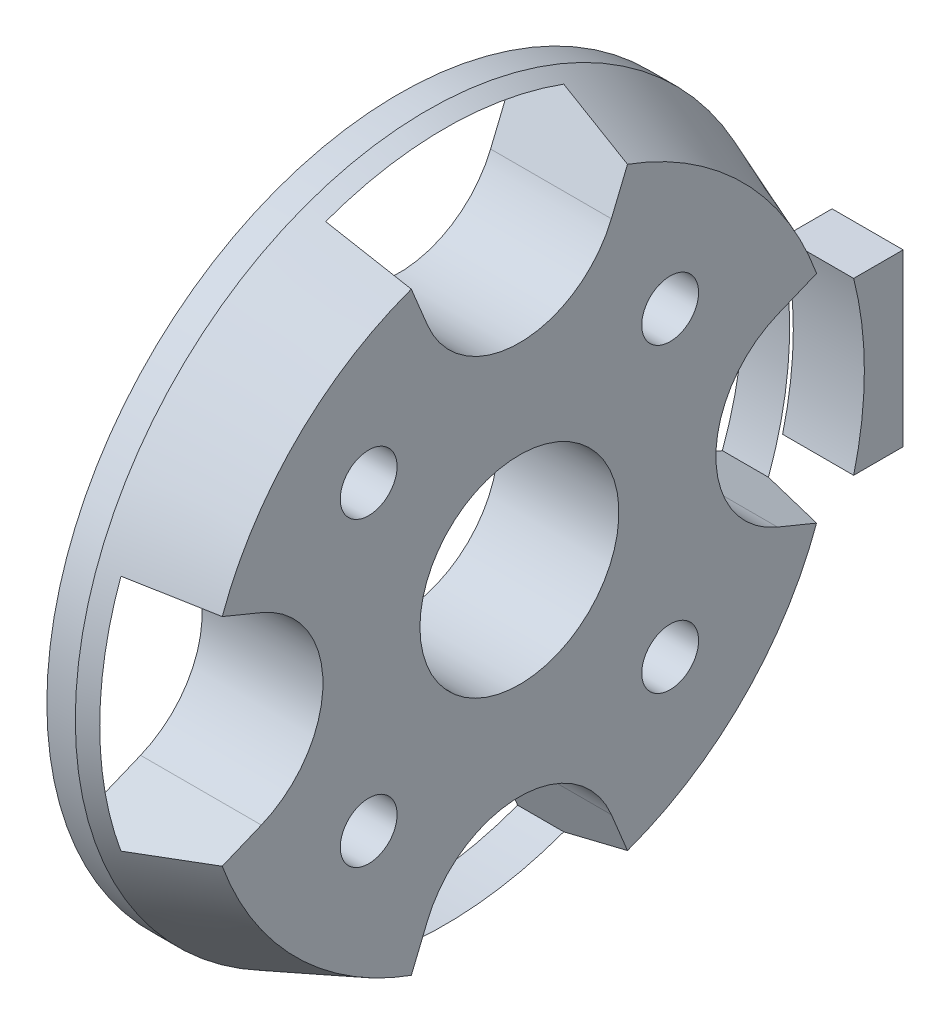
SolidWorks part; units mm, degrees
ref_plane "Front Plane" through (0, 0, 0) normal (0, 0, 1) x (1, 0, 0)
ref_plane "Top Plane" through (0, 0, 0) normal (0, 1, 0) x (1, 0, 0)
ref_plane "Right Plane" through (0, 0, 0) normal (1, 0, 0) x (0, 0, -1)
sketch "Sketch2" plane through (0, 0, 0) normal (0, 0, 1) x (1, 0, 0)
  line L0 (0, 0) -> (51.0154, 0) construction
  line L1 (0, 24.75) -> (2, 24.75)
  line L2 (2, 24.75) -> (8.5, 22.25)
  line L3 (8.5, 22.25) -> (8.5, 7)
  line L4 (8.5, 7) -> (0, 7)
  line L5 (0, 7) -> (0, 24.75)
  dimension "D1" = 8.5
  dimension "D2" = 2
  dimension "D3" = 2.5
  dimension "D4" = 14
  dimension "D5" = 49.5
revolve "Revolve1" add sketch "Sketch2" angle 360 about L0
sketch "Sketch3" plane through (8.5, 0, 0) normal (1, 0, 0) x (0, 0, -1)
  line L0 (0, 0) -> (10.6066, 10.6066) construction
  line L1 (0, 0) -> (5.0555, 0) construction
  circle A0 centre (10.6066, 10.6066) radius 2
  circle A1 centre (10.6066, -10.6066) radius 2
  circle A2 centre (-10.6066, -10.6066) radius 2
  circle A3 centre (-10.6066, 10.6066) radius 2
  point P14 (0, 0)
  dimension "D2" = 4
  dimension "D1" = 45
  dimension "D3" = 15
  dimension "D4" = 4
extrude "Cut-Extrude1" cut sketch "Sketch3" against normal blind 5
sketch "Sketch4" plane through (8.5, 0, 0) normal (1, 0, 0) x (0, 0, -1)
  line L0 (0, 0) -> (15, 0) construction
  line L1 (15, 6) -> (27, 6)
  line L2 (15, 6) -> (15, -6)
  line L3 (15, -6) -> (27, -6)
  line L4 (27, 6) -> (27, -6)
  dimension "D1" = 12
  dimension "D2" = 12
  dimension "D3" = 15
extrude "Boss-Extrude1" add sketch "Sketch4" against normal blind 5
sketch "Sketch6" plane through (8.5, 0, 0) normal (1, 0, 0) x (0, 0, -1)
  line L0 (8.8598, 93.3826) -> (181.5264, 93.3826) construction
  line L1 (-6.4723, 18.1576) -> (-7.606, 20.9096)
  line L2 (6.4723, 18.1576) -> (7.606, 20.9096)
  line L3 (0, 0) -> (0, 20.8239) construction
  line L4 (-7.606, 20.9096) -> (-8.3768, 22.7807)
  line L5 (7.606, 20.9096) -> (8.3768, 22.7807)
  arc A0 (-6.4723, 18.1576) -> (6.4723, 18.1576) centre (0, 20.8239) ccw
  arc A1 (-7.606, 20.9096) -> (7.606, 20.9096) centre (0, 0) cw construction
  arc A2 (21.4257, 6) -> (21.4257, -6) centre (0, 0) ccw construction
  arc A3 (8.3768, 22.7807) -> (-8.3768, 22.7807) centre (0, 0) ccw
  dimension "D1" = 7
  dimension "D2" = 5
extrude "Cut-Extrude2" cut sketch "Sketch6" against normal through all
pattern_circular "CirPattern1" count 4 over 360 about axis through (0, 0, 0) along (-1, 0, 0) of "Cut-Extrude2" reverse direction yes
